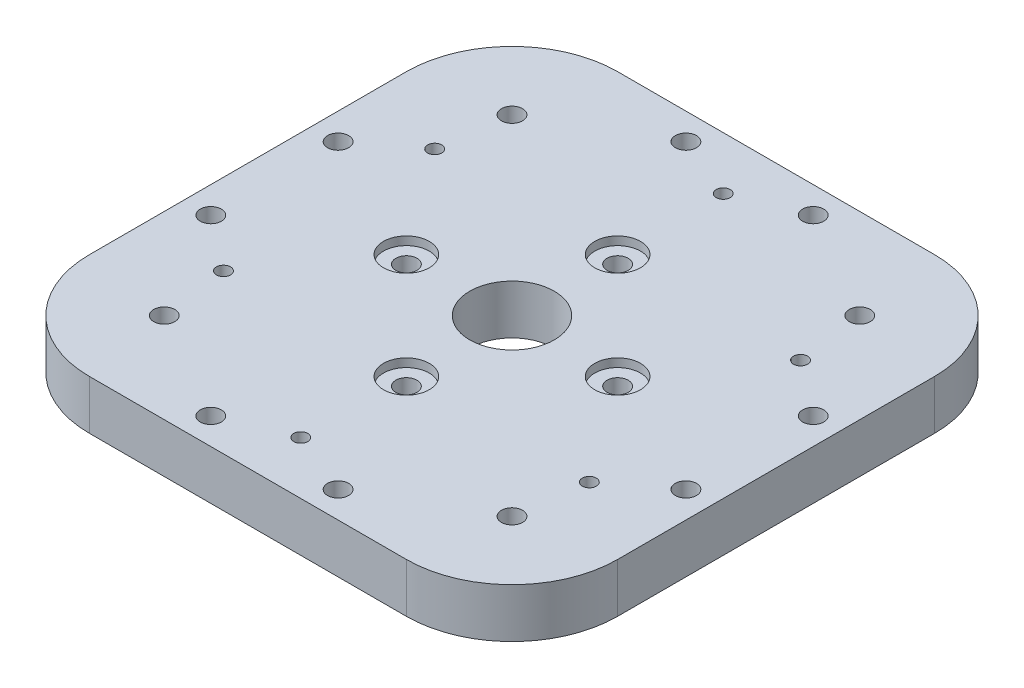
SolidWorks part; units mm, degrees
ref_plane "Front Plane" through (0, 0, 0) normal (0, 0, 1) x (1, 0, 0)
ref_plane "Top Plane" through (0, 0, 0) normal (0, 1, 0) x (1, 0, 0)
ref_plane "Right Plane" through (0, 0, 0) normal (1, 0, 0) x (0, 0, -1)
sketch "Sketch1" plane through (0, 0, 0) normal (0, 1, 0) x (1, 0, 0)
  line L0 (-49.4318, 0) -> (0, 0) construction
  line L1 (0, 0) -> (-47.2333, -12.6561) construction
  line L2 (-37.5, 37.5) -> (37.5, 37.5)
  line L3 (-37.5, 37.5) -> (-37.5, -37.5)
  line L4 (37.5, 37.5) -> (37.5, -37.5)
  line L5 (-37.5, -37.5) -> (37.5, -37.5)
  circle A0 centre (0, 0) radius 37.5 construction
  circle A1 centre (0, 0) radius 30 construction
  circle A2 centre (0, 0) radius 6
  circle A3 centre (0, 0) radius 15 construction
  circle A4 centre (0, 15) radius 1.5
  circle A5 centre (15, 0) radius 1.5
  circle A6 centre (0, -15) radius 1.5
  circle A7 centre (-15, 0) radius 1.5
  circle A11 centre (0, 0) radius 35 construction
  circle A12 centre (-33.737, -9.0398) radius 1.5
  circle A13 centre (-33.737, 9.0398) radius 1.5
  circle A14 centre (-24.6972, 24.6972) radius 1.5
  circle A15 centre (-9.0398, 33.737) radius 1.5
  circle A16 centre (9.0398, 33.737) radius 1.5
  circle A17 centre (24.6972, 24.6972) radius 1.5
  circle A18 centre (33.737, 9.0398) radius 1.5
  circle A19 centre (33.737, -9.0398) radius 1.5
  circle A20 centre (24.6972, -24.6972) radius 1.5
  circle A21 centre (9.0398, -33.737) radius 1.5
  circle A22 centre (-9.0398, -33.737) radius 1.5
  circle A23 centre (-24.6972, -24.6972) radius 1.5
  circle A24 centre (0, 30) radius 1
  circle A25 centre (25.9808, 15) radius 1
  circle A26 centre (25.9808, -15) radius 1
  circle A27 centre (0, -30) radius 1
  circle A28 centre (-25.9808, -15) radius 1
  circle A29 centre (-25.9808, 15) radius 1
  point P17 (0, 0)
  point P44 (0, 0)
  point P57 (0, 0)
  dimension "D1" = 75
  dimension "D2" = 60
  dimension "D3" = 12
  dimension "D4" = 3
  dimension "D6" = 30
  dimension "D7" = 70
  dimension "D9" = 3
  dimension "D11" = 2
  dimension "D8" = 15
  dimension "D5" = 4
  dimension "D10" = 12
  dimension "D12" = 6
extrude "Boss-Extrude1" add sketch "Sketch1" along normal blind 7
sketch "Sketch2" plane through (0, 7, 0) normal (0, 1, 0) x (1, 0, 0)
  circle A0 centre (0, 0) radius 15 construction
  circle A1 centre (0, 15) radius 3.25
  circle A2 centre (15, 0) radius 3.25
  circle A3 centre (0, -15) radius 3.25
  circle A4 centre (-15, 0) radius 3.25
  point P15 (0, 0)
  dimension "D1" = 6.5
  dimension "D2" = 4
extrude "Cut-Extrude1" cut sketch "Sketch2" against normal blind 1.2
fillet "Fillet1" radius 15 4 edges at (-37.5, 3.5, -37.5) (-37.5, 3.5, 37.5) (37.5, 3.5, 37.5) (37.5, 3.5, -37.5)
